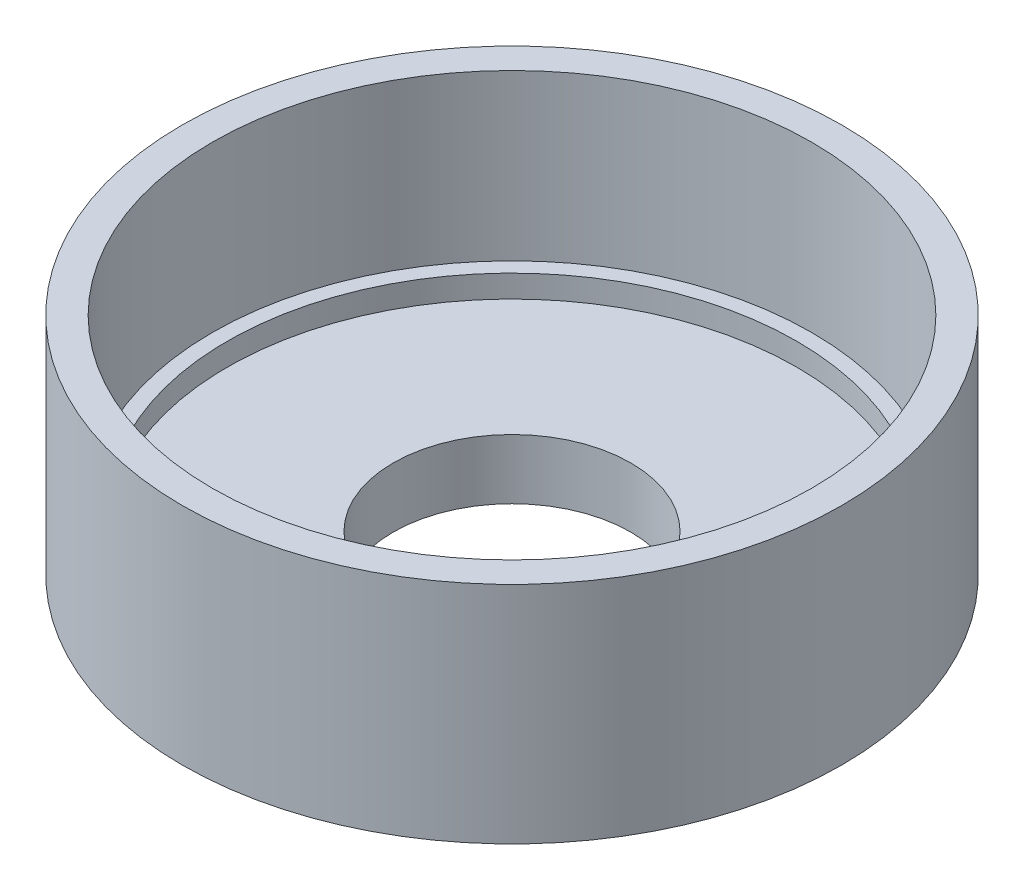
SolidWorks part; units mm, degrees
ref_plane "Front Plane" through (0, 0, 0) normal (0, 0, 1) x (1, 0, 0)
ref_plane "Top Plane" through (0, 0, 0) normal (0, 1, 0) x (1, 0, 0)
ref_plane "Right Plane" through (0, 0, 0) normal (1, 0, 0) x (0, 0, -1)
sketch "Sketch1" plane through (0, 0, 0) normal (0, 1, 0) x (1, 0, 0)
  circle A0 centre (0, 0) radius 20
  circle A1 centre (0, 0) radius 22
  circle A2 centre (0, 0) radius 7.93
  circle A3 centre (0, 0) radius 19
  dimension "D1" = 40
  dimension "D2" = 44
  dimension "D3" = 38
  dimension "D4" = 15.86
extrude "Boss-Extrude1" add sketch "Sketch1" against normal blind 4 contours A1 | A2
extrude "Boss-Extrude2" add sketch "Sketch1<3>" along normal blind 11 contours A0 | A1
sketch "Sketch1<3>" plane through (0, 0, 0) normal (0, 1, 0) x (1, 0, 0) same geometry as "Sketch1"
extrude "Cut-Extrude1" cut sketch "Sketch1<4>" against normal blind 1.5 contours A3
sketch "Sketch1<4>" plane through (0, 0, 0) normal (0, 1, 0) x (1, 0, 0) same geometry as "Sketch1"
sketch "Sketch3" plane through (0, -4, 0) normal (0, -1, 0) x (1, 0, 0)
  circle A0 centre (0, 0) radius 7.93 construction
  circle A1 centre (0, 0) radius 7.93
  circle A2 centre (0, 0) radius 11
  dimension "D1" = 22
extrude "Boss-Extrude3" add sketch "Sketch3" along normal blind 1.5
chamfer "Chamfer1" distance 2.5 angle 45 1 edges at (0, -5.5, -11)
